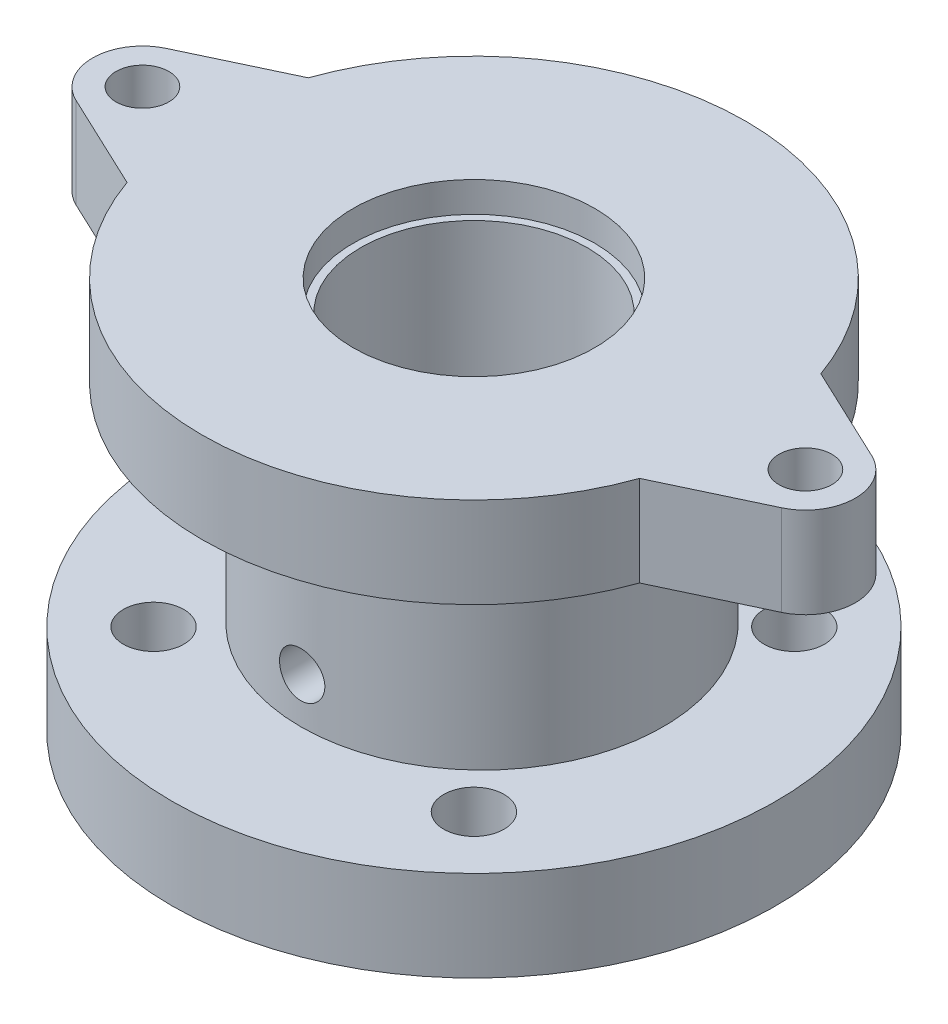
SolidWorks part; units mm, degrees
ref_plane "Front Plane" through (0, 0, 0) normal (0, 0, 1) x (1, 0, 0)
ref_plane "Top Plane" through (0, 0, 0) normal (0, 1, 0) x (1, 0, 0)
ref_plane "Right Plane" through (0, 0, 0) normal (1, 0, 0) x (0, 0, -1)
sketch "Sketch1" plane through (0, 0, 0) normal (0, 1, 0) x (1, 0, 0)
  circle A0 centre (0, 0) radius 7.5
  circle A1 centre (0, 0) radius 20
  dimension "D1" = 40
  dimension "D2" = 15
extrude "Boss-Extrude1" add sketch "Sketch1" along normal blind 6
sketch "Sketch2" plane through (0, 6, 0) normal (0, 1, 0) x (1, 0, 0)
  circle A0 centre (0, 0) radius 7.5
  circle A1 centre (0, 0.5354) radius 12
  dimension "D1" = 24
extrude "Boss-Extrude2" add sketch "Sketch2" along normal blind 14
sketch "Sketch3" plane through (0, 0, 0) normal (0, 0, 1) x (1, 0, 0)
  circle A0 centre (0, 9) radius 1.5
  dimension "D1" = 9
  dimension "D2" = 3
extrude "Cut-Extrude1" cut sketch "Sketch3" against normal through all both and the other way through all
sketch "Sketch4" plane through (0, 20, 0) normal (0, 1, 0) x (1, 0, 0)
  circle A0 centre (0, 0) radius 18
  circle A1 centre (0, 0) radius 7.5
  dimension "D1" = 36
extrude "Boss-Extrude3" add sketch "Sketch4" along normal blind 6
sketch "Sketch5" plane through (0, 26, 0) normal (0, 1, 0) x (1, 0, 0)
  line L0 (-21.95, 0) -> (21.95, 0) construction
  line L1 (-23.3588, 2.9842) -> (-16.9706, 6)
  line L2 (-23.3588, -2.9842) -> (-16.9706, -6)
  line L3 (23.3588, 2.9842) -> (16.9706, 6)
  line L4 (23.3588, -2.9842) -> (16.9706, -6)
  line L5 (-25.25, 0) -> (25.25, 0) construction
  circle A0 centre (-21.95, 0) radius 1.75
  circle A1 centre (21.95, 0) radius 1.75
  arc A2 (-23.3588, 2.9842) -> (-23.3588, -2.9842) centre (-21.95, 0) ccw
  arc A3 (23.3588, -2.9842) -> (23.3588, 2.9842) centre (21.95, 0) ccw
  arc A4 (-16.9706, 6) -> (-16.9706, -6) centre (0, 0) ccw
  arc A5 (16.9706, -6) -> (16.9706, 6) centre (0, 0) ccw
  circle A6 centre (0, 0) radius 18 construction
  point P3 (0, 0)
  point P14 (18, 0)
  point P15 (0, 0)
  point P16 (-18, 0)
  dimension "D2" = 3.5
  dimension "D3" = 3.5
  dimension "D1" = 43.9
  dimension "D4" = 12
  dimension "D5" = 50.5
extrude "Boss-Extrude4" add sketch "Sketch5" against normal up to surface (6 mm away) up to face at (0, 20, 11.4646)
sketch "Sketch6" plane through (0, 0, 0) normal (0, -1, 0) x (1, 0, 0)
  line L0 (0, 0) -> (-18.2577, 0) construction
  line L1 (0, 0) -> (-10.6066, 10.6066) construction
  circle A0 centre (-10.6066, 10.6066) radius 2
  circle A1 centre (10.6066, 10.6066) radius 2
  circle A2 centre (10.6066, -10.6066) radius 2
  circle A3 centre (-10.6066, -10.6066) radius 2
  point P14 (0, 0)
  dimension "D2" = 15
  dimension "D3" = 4
  dimension "D1" = 45
  dimension "D4" = 4
extrude "Cut-Extrude2" cut sketch "Sketch6" against normal up to surface (6 mm away) and the other way through all up to face at (0, 6, 20)
sketch "Sketch7" plane through (0, 26, 0) normal (0, 1, 0) x (1, 0, 0)
  circle A0 centre (0, 0) radius 8
  dimension "D1" = 16
extrude "Cut-Extrude3" cut sketch "Sketch7" against normal blind 2
ref_plane "Plane3" through (0, -192.3, 0) normal (0, -1, 0) x (-1, 0, 0)
sketch "Sketch10" plane through (0, -192.3, 0) normal (0, -1, 0) x (-1, 0, 0)
  point P0 (0, 0)
